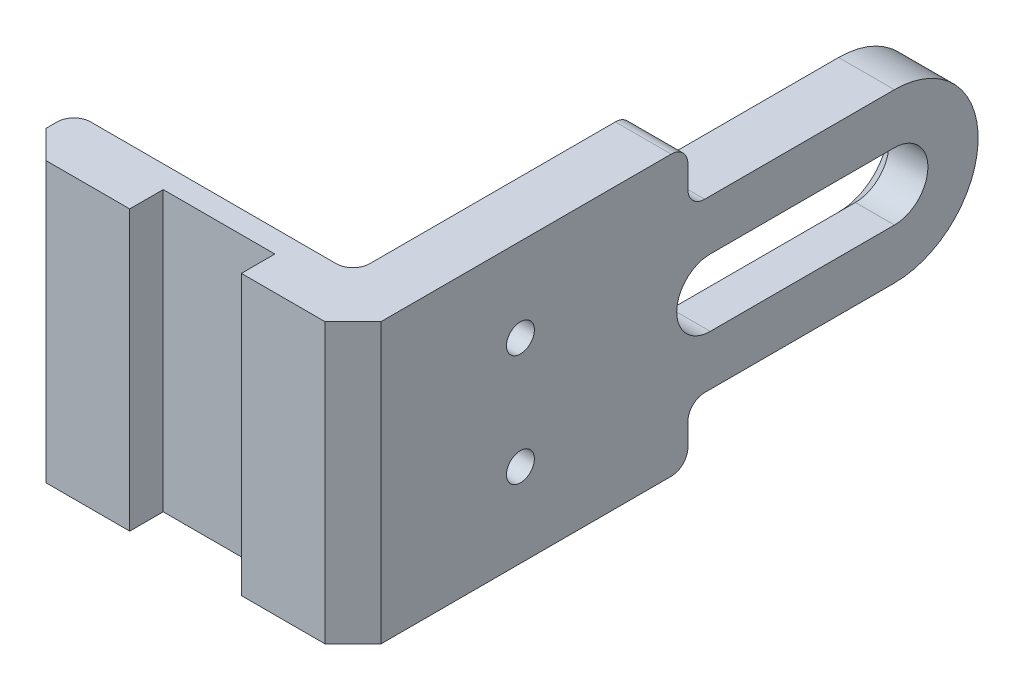
SolidWorks part; units mm, degrees
material "2014-T6"
ref_plane "Front Plane" through (0, 0, 0) normal (0, 0, 1) x (1, 0, 0)
ref_plane "Top Plane" through (0, 0, 0) normal (0, 1, 0) x (1, 0, 0)
ref_plane "Right Plane" through (0, 0, 0) normal (1, 0, 0) x (0, 0, -1)
sketch "Sketch1" plane through (0, 0, 0) normal (0, 1, 0) x (1, 0, 0)
  line L1 (0, 0) -> (-30, 0)
  line L2 (0, 0) -> (0, 10)
  line L3 (-5, 5) -> (-30, 5)
  line L4 (-30, 0) -> (-30, 5)
  line L5 (0, 0) -> (-5, 0)
  line L6 (0, 0) -> (0, 56)
  line L7 (0, 56) -> (-5, 56)
  line L8 (-5, 5) -> (-5, 56)
  dimension "D1" = 30
  dimension "D2" = 5
  dimension "D3" = 5
  dimension "D4" = 56
extrude "Boss-Extrude1" add sketch "Sketch1" along normal blind 25 contours L6 L7 L8 L3 L4 L1
sketch "Sketch2" plane through (0, 0, 0) normal (1, 0, 0) x (0, 0, -1)
  line L0 (0, 25) -> (56, 25) construction
  line L1 (30, 25) -> (56, 25)
  line L2 (30, 25) -> (30, 20)
  line L3 (30, 20) -> (56, 20)
  line L4 (56, 25) -> (56, 20)
  line L5 (56, 25) -> (56, 0) construction
  line L6 (0, 0) -> (56, 0) construction
  line L7 (30, 5) -> (56, 5)
  line L8 (30, 5) -> (30, 0)
  line L9 (30, 0) -> (56, 0)
  line L10 (56, 5) -> (56, 0)
  line L11 (0, 25) -> (0, 0) construction
  line L12 (0, 12.5) -> (97, 12.5) construction
  line L13 (56, 20) -> (56, 5)
  circle A0 centre (48.5, 12.5) radius 7.5
  dimension "D2" = 7.5
  dimension "D1" = 30
extrude "Cut-Extrude1" cut sketch "Sketch2" against normal blind 25 contours L4 L1 L2 L3 | A0 L13 L3 | A0 L7 L13 | L10 L7 L8 L9 region at (0, 22.5, -43) region at (0, 18.3247, -54.3247) region at (0, 6.6753, -54.3247) region at (0, 2.5, -43)
sketch "Sketch3" plane through (0, 0, 0) normal (1, 0, 0) x (0, 0, -1)
  line L0 (32, 12.5) -> (48.5, 12.5) construction
  line L1 (32, 15.5) -> (48.5, 15.5)
  line L2 (32, 9.5) -> (48.5, 9.5)
  line L3 (0, 12.5) -> (23.8442, 12.5) construction
  line L4 (0, 25) -> (0, 0) construction
  arc A0 (32, 15.5) -> (32, 9.5) centre (32, 12.5) ccw
  arc A1 (48.5, 9.5) -> (48.5, 15.5) centre (48.5, 12.5) ccw
  arc A2 (48.5, 5) -> (48.5, 20) centre (48.5, 12.5) ccw construction
  point P2 (40.25, 12.5)
  dimension "D1" = 3
  dimension "D2" = 32
  dimension "D3" = 48.5
extrude "Cut-Extrude2" cut sketch "Sketch3" against normal blind 25 contours L2 A1 L1 A0
fillet "Fillet1" radius 1.5 4 edges at (-2.5, 20, -30) (-2.5, 5, -30) (-2.5, 0, -30) (-2.5, 25, -30)
sketch "Sketch5" plane through (0, 0, 0) normal (1, 0, 0) x (0, 0, -1)
  line L0 (0, 0) -> (5, 0) construction
  line L1 (5, 25) -> (28.5, 25) construction
  circle A0 centre (15, 17.5) radius 3
  circle A1 centre (15, 7.5) radius 3
  circle A2 centre (15, 17.5) radius 1.25
  circle A3 centre (15, 7.5) radius 1.25
  dimension "D2" = 6
  dimension "D3" = 6
  dimension "D7" = 2.5
  dimension "D8" = 2.5
  dimension "D1" = 10
  dimension "D4" = 15
  dimension "D5" = 7.5
  dimension "D6" = 7.5
extrude "Cut-Extrude4" cut sketch "Sketch5" against normal blind 25 contours A2 | A3
extrude "Cut-Extrude5" cut sketch "Sketch5<4>" against normal blind 2.5 from offset 2.5 offset against normal yes
sketch "Sketch5<4>" plane through (0, 0, 0) normal (1, 0, 0) x (0, 0, -1) same geometry as "Sketch5"
sketch "Sketch7" plane through (0, 25, 0) normal (0, 1, 0) x (1, 0, 0)
  line L0 (0, 0) -> (-30, 0) construction
  line L1 (-20, 3) -> (-10, 3)
  line L2 (-20, 3) -> (-20, 0)
  line L3 (-20, 0) -> (-10, 0)
  line L4 (-10, 3) -> (-10, 0)
  line L5 (-30, 0) -> (-30, 5) construction
  dimension "D1" = 10
  dimension "D2" = 10
  dimension "D3" = 3
extrude "Cut-Extrude6" cut sketch "Sketch7" against normal through all contours L4 L3 L2 L1
chamfer "Chamfer1" distance 2.5 angle 45 2 edges at (0, 12.5, 0) (-30, 12.5, 0)
fillet "Fillet2" radius 1.5 2 edges at (-30, 12.5, -5) (-5, 12.5, -5)
chamfer "Chamfer2" distance 1.5 angle 45 4 edges at (-5, 9.5, -40.25) (-5, 12.5, -51.5) (-5, 12.5, -29) (-5, 15.5, -40.25)
